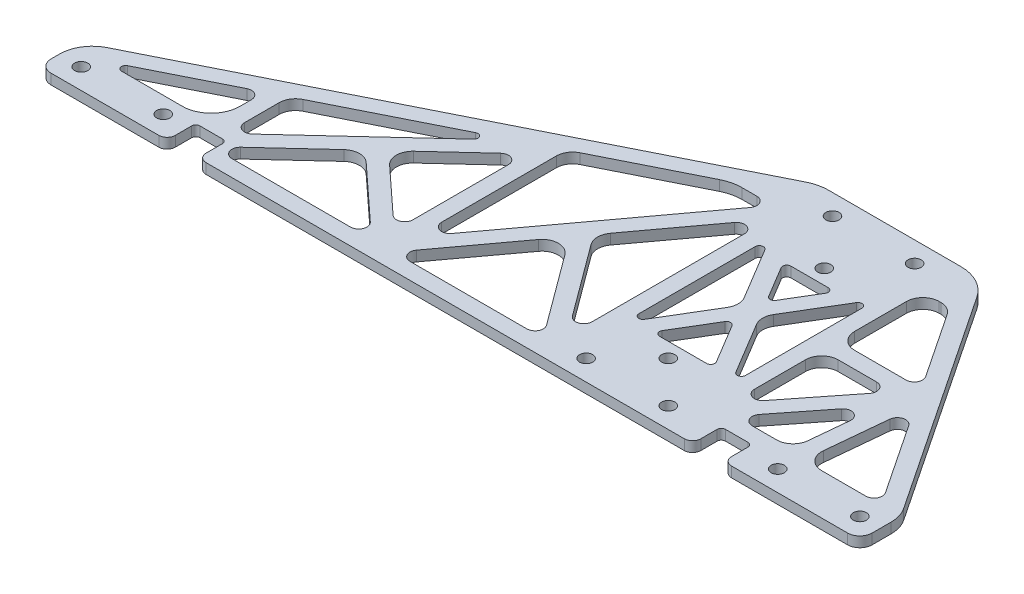
SolidWorks part; units mm, degrees
ref_plane "Front Plane" through (0, 0, 0) normal (0, 0, 1) x (1, 0, 0)
ref_plane "Top Plane" through (0, 0, 0) normal (0, 1, 0) x (1, 0, 0)
ref_plane "Right Plane" through (0, 0, 0) normal (1, 0, 0) x (0, 0, -1)
sketch "Sketch1" plane through (0, 0, 0) normal (0, 1, 0) x (1, 0, 0)
  line L0 (0, 0) -> (254, 0)
  line L2 (203.2, 88.9) -> (152.4, 88.9)
  line L4 (0, 0) -> (0, 12.7)
  line L5 (0, 12.7) -> (152.4, 88.9)
  line L6 (203.2, 88.9) -> (254, 12.7)
  line L7 (254, 12.7) -> (254, 0)
  line L8 (0, 6.35) -> (44.45, 6.35) construction
  line L9 (254, 6.35) -> (222.25, 6.35) construction
  line L10 (139.7, 82.55) -> (207.4333, 82.55) construction
  line L11 (44.45, 0) -> (44.45, 34.925) construction
  line L12 (156.6333, 12.7) -> (154.0933, 7.62)
  line L13 (224.7006, 47.4909) -> (221.314, 12.7) construction
  line L20 (127, 76.2) -> (211.6667, 76.2)
  line L21 (154.0933, 76.2) -> (101.6, 5.08) construction
  line L22 (154.0933, 12.7) -> (154.0933, 7.62)
  line L23 (247.8946, 12.7) -> (194.7333, 12.7)
  line L24 (224.7006, 47.4909) -> (197.2733, 12.7) construction
  line L28 (224.7006, 47.4909) -> (194.7333, 47.4909) construction
  line L31 (5.08, 9.5604) -> (153.5992, 83.82)
  line L32 (200.4813, 83.82) -> (153.5992, 83.82)
  line L33 (200.4813, 83.82) -> (248.92, 11.1619)
  line L34 (248.92, 11.1619) -> (248.92, 5.08)
  line L35 (5.08, 5.08) -> (248.92, 5.08)
  line L36 (5.08, 5.08) -> (5.08, 9.5604)
  line L37 (101.6, 5.08) -> (101.6, 57.8204) construction
  line L39 (127.8467, 40.64) -> (154.0933, 5.08) construction
  line L40 (101.6, 57.8204) -> (44.45, 5.08) construction
  line L41 (73.025, 31.4502) -> (101.6, 5.08) construction
  line L42 (154.0933, 7.62) -> (154.0933, 5.08)
  line L83 (152.8233, 5.08) -> (150.2833, 0)
  line L84 (125.803, 39.1316) -> (152.0497, 3.5716)
  line L107 (152.0497, 77.7084) -> (99.5564, 6.5884)
  line L108 (156.6333, 76.2) -> (194.7333, 12.7) construction
  line L113 (194.7333, 76.2) -> (156.6333, 12.7) construction
  line L117 (104.14, 5.08) -> (104.14, 63.6207)
  line L118 (156.6333, 12.7) -> (194.7333, 12.7)
  line L119 (194.7333, 12.7) -> (201.0833, 0)
  line L120 (154.0933, 6.35) -> (197.9083, 6.35) construction
  line L126 (192.5553, 77.5068) -> (154.4553, 14.0068)
  line L127 (154.4553, 74.8932) -> (192.5553, 11.3932)
  line L128 (156.6333, 12.7) -> (156.6333, 76.2) construction
  line L129 (194.7333, 12.7) -> (194.7333, 76.2) construction
  line L130 (197.2733, 12.7) -> (197.2733, 76.2)
  line L131 (159.1733, 12.7) -> (159.1733, 76.2)
  line L132 (192.1933, 12.7) -> (192.1933, 76.2)
  line L133 (154.0933, 12.7) -> (154.0933, 76.2)
  line L147 (196.9114, 74.8932) -> (158.8114, 11.3932)
  line L148 (158.8114, 77.5068) -> (196.9114, 14.0068)
  line L154 (104.14, 63.6207) -> (42.7274, 6.9466)
  line L155 (71.3024, 29.5836) -> (99.8774, 3.2134)
  line L156 (224.7006, 50.0309) -> (194.7333, 50.0309)
  line L157 (222.7059, 49.0635) -> (195.2786, 14.2725)
  line L158 (197.2733, 12.7) -> (197.2733, 7.62)
  line L159 (222.1726, 47.737) -> (218.7859, 12.9461)
  line L160 (129.8903, 42.1484) -> (156.137, 6.5884)
  line L163 (156.137, 74.6916) -> (103.6436, 3.5716)
  line L164 (99.06, 5.08) -> (99.06, 52.0201)
  line L165 (99.06, 52.0201) -> (46.1726, 3.2134)
  line L166 (175.6833, 19.05) -> (162.9833, 6.35) construction
  line L167 (175.6833, 19.05) -> (188.3833, 6.35) construction
  line L168 (162.9833, 82.55) -> (175.6833, 67.31) construction
  line L169 (175.6833, 67.31) -> (188.3833, 82.55) construction
  line L170 (161.6625, 21.082) -> (189.7041, 21.082) construction
  line L171 (161.6625, 23.622) -> (189.7041, 23.622)
  line L172 (163.1865, 65.278) -> (188.1801, 65.278) construction
  line L173 (163.1865, 62.738) -> (188.1801, 62.738)
  line L174 (74.7476, 33.3168) -> (103.3226, 6.9466)
  line L175 (224.7006, 44.9509) -> (194.7333, 44.9509)
  line L176 (226.6953, 45.9184) -> (199.268, 11.1275)
  line L177 (227.2287, 47.2449) -> (223.842, 12.4539)
  line L178 (8.8192, 11.43) -> (44.45, 11.43)
  line L179 (46.99, 0) -> (46.99, 34.925)
  line L180 (41.91, 0) -> (41.91, 34.925)
  line L181 (198.2745, 13.97) -> (221.4376, 13.97)
  circle A0 centre (6.7733, 6.35) radius 2.032
  circle A1 centre (32.1733, 6.35) radius 2.032
  circle A2 centre (222.25, 6.35) radius 2.032
  circle A3 centre (247.65, 6.35) radius 2.032
  circle A4 centre (162.9833, 82.55) radius 2.032
  circle A5 centre (188.3833, 82.55) radius 2.032
  circle A28 centre (162.9833, 6.35) radius 2.032
  circle A29 centre (188.3833, 6.35) radius 2.032
  arc A32 (197.2733, 12.7) -> (192.1933, 12.7) centre (194.7333, 12.7) cw
  arc A33 (197.2733, 76.2) -> (192.1933, 76.2) centre (194.7333, 76.2) ccw
  arc A34 (159.1733, 12.7) -> (154.0933, 12.7) centre (156.6333, 12.7) cw
  arc A35 (159.1733, 76.2) -> (154.0933, 76.2) centre (156.6333, 76.2) ccw
  arc A45 (192.5553, 77.5068) -> (196.9114, 74.8932) centre (194.7333, 76.2) cw
  arc A46 (154.4553, 14.0068) -> (158.8114, 11.3932) centre (156.6333, 12.7) ccw
  arc A47 (154.4553, 74.8932) -> (158.8114, 77.5068) centre (156.6333, 76.2) cw
  arc A48 (192.5553, 11.3932) -> (196.9114, 14.0068) centre (194.7333, 12.7) ccw
  circle A59 centre (175.6833, 19.05) radius 2.032
  circle A60 centre (175.6833, 67.31) radius 2.032
  arc A61 (125.803, 39.1316) -> (129.8903, 42.1484) centre (127.8467, 40.64) cw
  arc A62 (152.0497, 3.5716) -> (156.137, 6.5884) centre (154.0933, 5.08) ccw
  arc A63 (152.0497, 77.7084) -> (156.137, 74.6916) centre (154.0933, 76.2) cw
  arc A64 (99.5564, 6.5884) -> (103.6436, 3.5716) centre (101.6, 5.08) ccw
  arc A65 (104.14, 5.08) -> (99.06, 5.08) centre (101.6, 5.08) cw
  arc A66 (42.7274, 6.9466) -> (46.1726, 3.2134) centre (44.45, 5.08) ccw
  arc A67 (71.3024, 29.5836) -> (74.7476, 33.3168) centre (73.025, 31.4502) cw
  arc A68 (99.8774, 3.2134) -> (103.3226, 6.9466) centre (101.6, 5.08) ccw
  arc A69 (224.7006, 50.0309) -> (224.7006, 44.9509) centre (224.7006, 47.4909) cw
  arc A70 (194.7333, 50.0309) -> (194.7333, 44.9509) centre (194.7333, 47.4909) ccw
  arc A71 (222.7059, 49.0635) -> (226.6953, 45.9184) centre (224.7006, 47.4909) cw
  arc A72 (195.2786, 14.2725) -> (199.268, 11.1275) centre (197.2733, 12.7) ccw
  arc A73 (222.1726, 47.737) -> (227.2287, 47.2449) centre (224.7006, 47.4909) cw
  arc A74 (218.7859, 12.9461) -> (223.842, 12.4539) centre (221.314, 12.7) ccw
  arc A75 (46.99, 0) -> (41.91, 0) centre (44.45, 0) cw
  arc A76 (46.99, 34.925) -> (41.91, 34.925) centre (44.45, 34.925) ccw
  dimension "D7" = 4.064
  dimension "D8" = 25.4
  dimension "D9" = 130.81
  dimension "D10" = 25.4
  dimension "D11" = 6.35
  dimension "D13" = 19.05
  dimension "D1" = 254
  dimension "D2" = 50.8
  dimension "D3" = 88.9
  dimension "D4" = 152.4
  dimension "D5" = 12.7
  dimension "D6" = 6.35
  dimension "D12" = 25.4
  dimension "D14" = 44.45
  dimension "D15" = 12.7
  dimension "D16" = 57.15
  dimension "D18" = 12.7
  dimension "D19" = 2.54
  dimension "D20" = 50.8
  dimension "D21" = 25.4
  dimension "D22" = 2.54
  dimension "D23" = 6.35
  dimension "D24" = 2.54
  dimension "D29" = 6.35
  dimension "D30" = 38.1
  dimension "D31" = 25.4
  dimension "D32" = 6.35
  dimension "D33" = 2.54
  dimension "D36" = 12.7
  dimension "D38" = 15.24
  dimension "D39" = 2.54
  dimension "D40" = 2.54
  dimension "D27" = 1.27
  dimension "D17" = 5.08
  dimension "D25" = 2.54
  dimension "D26" = 2.54
  dimension "D37" = 2.54
extrude "Boss-Extrude1" add sketch "Sketch1" along normal blind 3.175 contours L0 L7 L6 L2 L5 L4 | A0 | A1 | A5 | A4 | A2 | A3
extrude "Cut-Extrude2" cut sketch "Sketch1<3>" along normal through all contours L154 L31 L11 | L155 L165 L35 | L165 L174 L164 | L117 L107 L20 L31 | L84 L163 L35 | L133 L163 L160 L22 | L157 L175 L130 | L156 L33 L20 L130 | L147 L148 L132 | L131 L126 L127 | L173 L148 L126 | L147 L171 L127 | L33 L177 L23 | L178 L180 L31 | L176 L181 L159 | A28 | A59 | A29 | A60 region at (30.8797, 0, -16.9451) region at (73.025, 0, -12.718) region at (62.4687, 0, -31.7097) region at (120.7695, 0, -51.2726) region at (127.8467, 0, -15.5076) region at (91.6301, 0, -31.4502) region at (206.5243, 0, -60.8789) region at (146.3968, 0, -40.64) region at (204.6702, 0, -35.5682) region at (175.6833, 0, -28.919) region at (187.6774, 0, -44.45) region at (213.9093, 0, -22.3524) region at (163.6893, 0, -44.45) region at (232.896, 0, -23.1836) region at (175.6833, 0, -58.2876)
sketch "Sketch1<3>" plane through (0, 0, 0) normal (0, 1, 0) x (1, 0, 0) same geometry as "Sketch1"
fillet "Fillet1" radius 3.81 2 edges at (254, 1.5875, 0) (0, 1.5875, 0)
fillet "Fillet2" radius 10.16 2 edges at (254, 1.5875, -12.7) (0, 1.5875, -12.7)
fillet "Fillet3" radius 12.7 2 edges at (203.2, 1.5875, -88.9) (152.4, 1.5875, -88.9)
fillet "Fillet4" radius 1.27 12 edges at (159.1733, 1.5875, -67.0298) (192.1933, 1.5875, -67.0298) (192.1933, 1.5875, -21.8702) (159.1733, 1.5875, -21.8702) (183.694, 1.5875, -62.738) (167.6727, 1.5875, -62.738) (175.6833, 1.5875, -49.3869) (185.218, 1.5875, -23.622) (166.1487, 1.5875, -23.622) (175.6833, 1.5875, -39.5131) (93.426, 1.5875, -53.7334) (8.8192, 1.5875, -11.43)
fillet "Fillet5" radius 2.54 19 edges at (223.0073, 1.5875, -50.0309) (247.8946, 1.5875, -12.7) (226.9275, 1.5875, -44.1507) (221.3335, 1.5875, -39.1171) (197.2733, 1.5875, -16.8027) (219.4639, 1.5875, -44.9509) (104.14, 1.5875, -12.7984) (99.06, 1.5875, -52.0201) (48.1953, 1.5875, -5.08) (97.8547, 1.5875, -5.08) (99.06, 1.5875, -10.8803) (104.7569, 1.5875, -5.08) (150.9364, 1.5875, -5.08) (154.0933, 1.5875, -9.3572) (154.0933, 1.5875, -71.9228) (150.9364, 1.5875, -76.2) (41.91, 1.5875, -27.9754) (46.99, 1.5875, -10.8803) (201.5089, 1.5875, -13.97)
fillet "Fillet6" radius 5.08 14 edges at (172.7212, 1.5875, -44.45) (178.6455, 1.5875, -44.45) (223.866, 1.5875, -12.7) (197.2733, 1.5875, -50.0309) (197.2733, 1.5875, -44.9509) (197.2733, 1.5875, -76.2) (205.5613, 1.5875, -76.2) (73.025, 1.5875, -27.9939) (76.7703, 1.5875, -31.4502) (104.14, 1.5875, -59.0904) (131.0036, 1.5875, -40.64) (127.8467, 1.5875, -36.3628) (46.99, 1.5875, -30.5154) (218.8856, 1.5875, -13.97)
fillet "Fillet7" radius 12.7 1 edges at (138.3592, 1.5875, -76.2)
fillet "Fillet10" radius 8.89 1 edges at (41.91, 1.5875, -11.43)
sketch "Sketch2" plane through (0, 3.175, 0) normal (0, 1, 0) x (1, 0, 0)
  line L0 (39.6875, 0) -> (39.6875, 8.89)
  line L1 (3.81, 0) -> (250.19, 0) construction
  line L2 (39.6875, 8.89) -> (49.2125, 8.89)
  line L3 (49.2125, 8.89) -> (49.2125, 0)
  line L4 (0, 3.81) -> (0, 6.4208) construction
  line L5 (202.2475, 0) -> (202.2475, 8.89)
  line L6 (202.2475, 8.89) -> (211.7725, 8.89)
  line L7 (211.7725, 8.89) -> (211.7725, 0)
  line L8 (254, 9.6238) -> (254, 3.81) construction
  line L9 (3.81, 0) -> (250.19, 0)
  dimension "D1" = 39.6875
  dimension "D2" = 9.525
  dimension "D3" = 8.89
  dimension "D4" = 42.2275
extrude "Cut-Extrude3" cut sketch "Sketch2" against normal through all contours L0 L9 L3 L2 | L5 L9 L7 L6 region at (207.01, 3.175, -4.445) region at (44.45, 3.175, -4.445)
fillet "Fillet8" radius 1.27 4 edges at (211.7725, 1.5875, -8.89) (202.2475, 1.5875, -8.89) (49.2125, 1.5875, -8.89) (39.6875, 1.5875, -8.89)
fillet "Fillet9" radius 2.54 4 edges at (49.2125, 1.5875, 0) (39.6875, 1.5875, 0) (211.7725, 1.5875, 0) (202.2475, 1.5875, 0)
sketch "Sketch3" plane through (0, 3.175, 0) normal (0, 1, 0) x (1, 0, 0)
  line L0 (322.9659, 17.0563) -> (167.3565, 52.0385) construction
  circle A0 centre (322.9659, 17.0563) radius 2.286 construction
  circle A1 centre (322.9659, 17.0563) radius 2.286
  circle A2 centre (165.5654, 42.8079) radius 2.286
  arc A4 (167.3565, 52.0385) -> (163.5668, 11.5798) centre (322.9659, 17.0563) ccw construction
  dimension "D1" = 159.4931
  dimension "D2" = 4.572
extrude "Cut-Extrude4" cut sketch "Sketch3" against normal up to surface (3.175 mm away) contours A2 rebuild error yes up to face at (233.1564, 0, -22.5815)
